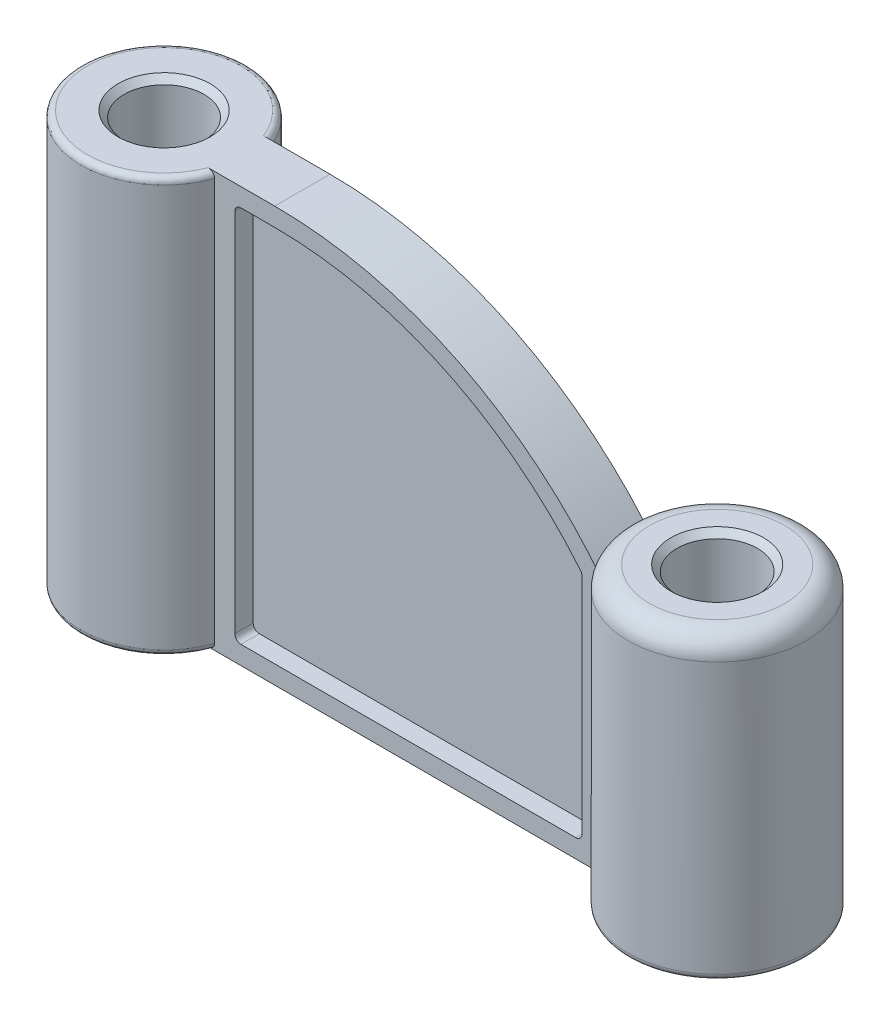
SolidWorks part; units mm, degrees
ref_plane "Спереди" through (0, 0, 0) normal (0, 0, 1) x (1, 0, 0)
ref_plane "Сверху" through (0, 0, 0) normal (0, 1, 0) x (1, 0, 0)
ref_plane "Справа" through (0, 0, 0) normal (1, 0, 0) x (0, 0, -1)
sketch "Эскиз1" plane through (0, 0, 0) normal (0, 0, 1) x (1, 0, 0)
  line L0 (-64, 0) -> (64, 0)
  line L1 (62, 2) -> (62, 90)
  line L2 (69, 97) -> (91, 97)
  line L3 (91, 97) -> (91, 0)
  line L4 (91, 0) -> (64, 0)
  line L5 (-62, 2) -> (-62, 133)
  line L6 (-64, 135) -> (-89, 135)
  line L7 (-89, 135) -> (-89, 0)
  line L8 (-89, 0) -> (-64, 0)
  line L9 (-64, 135) -> (-44, 135)
  line L10 (-44, 129) -> (-44, 0)
  line L11 (56, 80.7775) -> (56, 8)
  line L12 (54, 6) -> (-55, 6)
  line L13 (-57, 8) -> (-57, 127)
  line L14 (-44, 129) -> (-55, 129)
  line L15 (-44, 135) -> (-64, 135)
  arc A0 (62, 83.6002) -> (-44, 135) centre (-44, 0) ccw
  arc A1 (55.5433, 82.0496) -> (-44, 129) centre (-44, 0) ccw
  arc A2 (54, 6) -> (56, 8) centre (54, 8) ccw
  arc A3 (56, 80.7775) -> (55.5433, 82.0496) centre (54, 80.7775) ccw
  arc A4 (-57, 8) -> (-55, 6) centre (-55, 8) ccw
  arc A5 (-55, 129) -> (-57, 127) centre (-55, 127) ccw
  arc A6 (69, 97) -> (62, 90) centre (69, 90) ccw
  arc A7 (62, 2) -> (64, 0) centre (64, 2) ccw
  arc A8 (-64, 0) -> (-62, 2) centre (-64, 2) ccw
  arc A9 (-62, 133) -> (-64, 135) centre (-64, 133) ccw
  arc A10 (62, 83.6002) -> (91, 0) centre (-44, 0) cw
  dimension "D5" = 270
  dimension "D8" = 2
  dimension "D12" = 2
  dimension "D13" = 2
  dimension "D9" = 2
  dimension "D11" = 7
  dimension "D17" = 2
  dimension "D18" = 2
  dimension "D19" = 2
  dimension "D1" = 135
  dimension "D2" = 180
  dimension "D3" = 97
  dimension "D4" = 135
  dimension "D6" = 6
  dimension "D7" = 6
  dimension "D10" = 25
  dimension "D14" = 35
  dimension "D15" = 32
  dimension "D16" = 29
revolve "Повернуть1" add sketch "Эскиз1" angle 360 about L7 region at (-75.5062, 67.5, 0)
revolve "Повернуть2" add sketch "Эскиз1<4>" angle 360 about L3 region at (80.634, 72.0621, 0)
sketch "Эскиз1<4>" plane through (0, 0, 0) normal (0, 0, 1) x (1, 0, 0) same geometry as "Эскиз1"
extrude "Бобышка-Вытянуть1" add sketch "Эскиз1<5>" along normal blind 9 and the other way blind 9 contours A9 L5 A8 L0 L12 A4 L13 A5 L14 A1 A3 L11 A2 A7 L1 A0 L9 | L5 A9 L6 L7 L8 A8 | L1 A7 L4 L3 region at (-62.4542, 0.4542, 0) region at (-75.5062, 67.5, 0) region at (73.7197, 31.8699, 0)
sketch "Эскиз1<5>" plane through (0, 0, 0) normal (0, 0, 1) x (1, 0, 0) same geometry as "Эскиз1"
extrude "Бобышка-Вытянуть2" add sketch "Эскиз1<6>" along normal blind 3 and the other way blind 3 contours L11 A3 A1 L10 L12 A2 | L14 A5 L13 A4 L12 L10 region at (-50.4935, 67.5, 0) region at (2.5328, 61.1353, 0)
sketch "Эскиз1<6>" plane through (0, 0, 0) normal (0, 0, 1) x (1, 0, 0) same geometry as "Эскиз1"
sketch "Эскиз2" plane through (0, 0, 0) normal (0, 1, 0) x (1, 0, 0)
  line L0 (-116, 0) -> (120, 0) construction
  line L1 (-89, 25) -> (-89, -25) construction
  line L2 (91, 22) -> (91, -22) construction
  circle A0 centre (-89, 0) radius 27 construction
  circle A1 centre (91, 0) radius 29 construction
  circle A2 centre (-89, 0) radius 25 construction
  circle A3 centre (91, 0) radius 22 construction
  circle A4 centre (-89, 0) radius 13
  circle A5 centre (91, 0) radius 13.1009
  dimension "D1" = 26
  dimension "D2" = 26.2018
extrude "Вырез-Вытянуть7" cut sketch "Эскиз2" along normal through all
chamfer "Фаска4" distance 2 angle 45 2 edges at (104.1009, 97, 0) (91, 0, 13.1009)
chamfer "Фаска5" distance 2 angle 45 2 edges at (-89, 0, 13) (-89, 135, 13)
equation "\"A\"= 135мм"
equation "\"B\"= 58мм"
equation "\"C\"= 180мм"
equation "\"D\"= 26мм"
equation "\"Y\"= 1.5 * \"B\" + 10мм"
equation "\"D1@Эскиз1\"=\"A\""
equation "\"D2@Эскиз1\"=\"C\""
equation "\"D3@Эскиз1\"=\"Y\""
equation "\"D4@Эскиз1\"=\"A\""
equation "\"D1@Эскиз2\"=\"D\""
